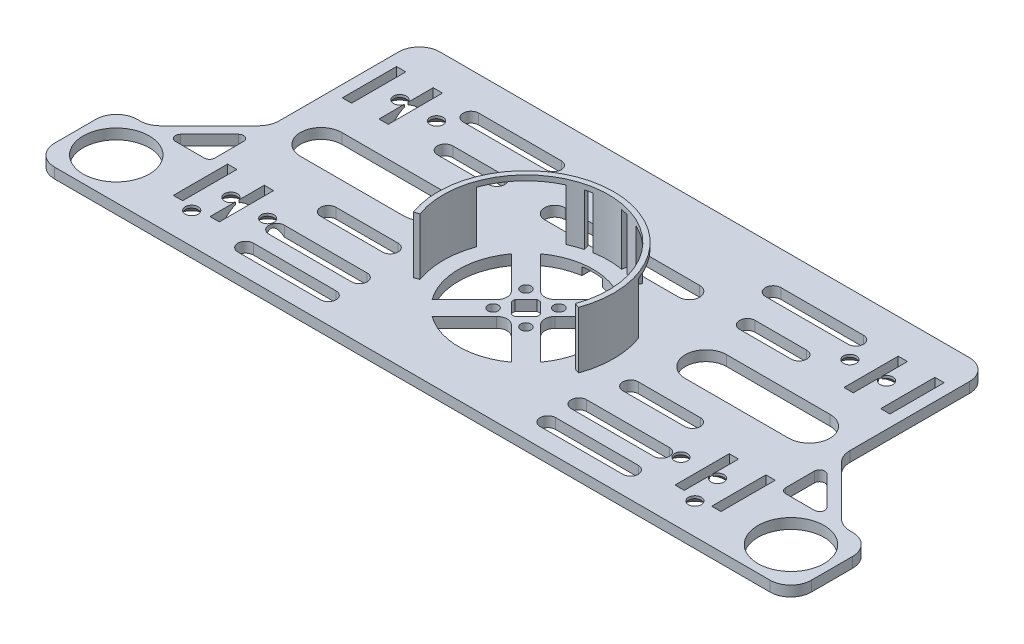
SolidWorks part; units mm, degrees
ref_plane "前视基准面" through (0, 0, 0) normal (0, 0, 1) x (1, 0, 0)
ref_plane "上视基准面" through (0, 0, 0) normal (0, 1, 0) x (1, 0, 0)
ref_plane "右视基准面" through (0, 0, 0) normal (1, 0, 0) x (0, 0, -1)
sketch "草图1" plane through (0, 0, 0) normal (0, 1, 0) x (1, 0, 0)
  line L0 (0, 0) -> (0, 46.1677) construction
  line L1 (-73.25, 0) -> (73.25, 0)
  line L2 (73.25, 0) -> (73.25, 16)
  line L8 (-73.25, 0) -> (-73.25, 16)
  line L9 (73.25, 16) -> (67.0784, 16)
  line L11 (55.25, 16) -> (55.25, 25)
  line L12 (55.25, 56.6) -> (-55.25, 56.6)
  line L13 (-55.25, 16) -> (-55.25, 25)
  line L14 (-73.25, 16) -> (-67.0784, 16)
  line L15 (64.25, 16) -> (55.25, 25)
  line L16 (67.0784, 16) -> (55.25, 27.8284)
  line L17 (55.25, 27.8284) -> (55.25, 56.6)
  line L18 (64.25, 16) -> (55.25, 16)
  line L19 (-67.0784, 16) -> (-55.25, 27.8284)
  line L20 (-64.25, 16) -> (-55.25, 25)
  line L21 (-64.25, 16) -> (-55.25, 16)
  line L22 (-55.25, 27.8284) -> (-55.25, 56.6)
  line L23 (0, 22) -> (7.4008, 22) construction
  line L24 (0, 22) -> (9.4181, 31.4181) construction
  line L25 (-10.4972, 29.6687) -> (7.6687, 11.5028)
  line L26 (10.4972, 14.3313) -> (-7.6687, 32.4972)
  line L27 (-10.4972, 14.3313) -> (7.6687, 32.4972)
  line L28 (10.4972, 29.6687) -> (-7.6687, 11.5028)
  line L29 (51.2, 17.25) -> (53, 6.75) construction
  line L30 (51.2, 17.25) -> (53, 17.25)
  line L31 (51.2, 17.25) -> (51.2, 6.75)
  line L32 (51.2, 6.75) -> (53, 6.75)
  line L33 (53, 17.25) -> (53, 6.75)
  line L34 (-51.2, 6.75) -> (-53, 6.75)
  line L35 (-53, 17.25) -> (-53, 6.75)
  line L36 (-51.2, 17.25) -> (-53, 17.25)
  line L37 (-51.2, 17.25) -> (-51.2, 6.75)
  line L38 (52.1, 0) -> (52.1, 56.6) construction
  line L39 (51.2, 49.95) -> (53, 39.45) construction
  line L40 (51.2, 49.95) -> (53, 49.95)
  line L41 (51.2, 49.95) -> (51.2, 39.45)
  line L42 (51.2, 39.45) -> (53, 39.45)
  line L43 (53, 49.95) -> (53, 39.45)
  line L44 (-51.2, 49.95) -> (-53, 39.45) construction
  line L45 (-51.2, 49.95) -> (-51.2, 39.45)
  line L46 (-51.2, 39.45) -> (-53, 39.45)
  line L47 (-53, 49.95) -> (-53, 39.45)
  line L48 (-51.2, 49.95) -> (-53, 49.95)
  line L49 (44.1, 17.25) -> (45.9, 17.25)
  line L50 (44.1, 17.25) -> (44.1, 6.75)
  line L51 (44.1, 6.75) -> (45.9, 6.75)
  line L52 (45.9, 17.25) -> (45.9, 6.75)
  line L53 (44.1, 49.95) -> (45.9, 49.95)
  line L54 (44.1, 49.95) -> (44.1, 39.45)
  line L55 (44.1, 39.45) -> (45.9, 39.45)
  line L56 (45.9, 49.95) -> (45.9, 39.45)
  line L57 (44.1, 49.95) -> (45.9, 39.45)
  line L58 (44.1, 17.25) -> (45.9, 6.75)
  line L59 (45, 56.6) -> (45, 0) construction
  line L60 (-44.1, 17.25) -> (-44.1, 6.75)
  line L61 (-44.1, 6.75) -> (-45.9, 6.75)
  line L62 (-45.9, 17.25) -> (-45.9, 6.75)
  line L63 (-44.1, 17.25) -> (-45.9, 17.25)
  line L64 (-44.1, 49.95) -> (-44.1, 39.45)
  line L65 (-44.1, 39.45) -> (-45.9, 39.45)
  line L66 (-45.9, 49.95) -> (-45.9, 39.45)
  line L67 (-44.1, 49.95) -> (-45.9, 49.95)
  line L68 (-52.1, 0) -> (-52.1, 56.6) construction
  line L69 (-45, 56.6) -> (-45, 0) construction
  line L70 (-13, 40.6) -> (13, 40.6) construction
  line L71 (-13, 42.6) -> (13, 42.6)
  line L72 (-13, 38.6) -> (13, 38.6)
  circle A2 centre (65.3, 8) radius 6.4
  circle A3 centre (-65.3, 8) radius 6.4
  circle A4 centre (0, 22) radius 4.5 construction
  circle A5 centre (3.182, 25.182) radius 1
  circle A6 centre (3.182, 18.818) radius 1
  circle A7 centre (-3.182, 18.818) radius 1
  circle A8 centre (-3.182, 25.182) radius 1
  circle A9 centre (0, 22) radius 13
  circle A11 centre (0, 22) radius 2.5
  arc A12 (-13, 42.6) -> (-13, 38.6) centre (-13, 40.6) ccw
  arc A13 (13, 38.6) -> (13, 42.6) centre (13, 40.6) ccw
  circle A14 centre (48.7, 6) radius 1
  circle A15 centre (-48.7, 6) radius 1
  point P3 (0, 56.6)
  point P18 (0, 0)
  point P19 (73.25, 8)
  point P26 (0, 22)
  point P55 (52.1, 12)
  point P66 (52.1, 44.7)
  point P67 (53, 44.7)
  point P68 (53, 12)
  point P85 (45, 44.7)
  point P100 (0, 40.6)
  dimension "D1" = 12.8
  dimension "D5" = 110.5
  dimension "D12" = 9
  dimension "D13" = 2
  dimension "D15" = 26
  dimension "D16" = 2
  dimension "D17" = 5
  dimension "D31" = 16
  dimension "D33" = 2
  dimension "D2" = 130.6
  dimension "D3" = 146.5
  dimension "D4" = 16
  dimension "D6" = 45
  dimension "D7" = 2
  dimension "D8" = 9
  dimension "D9" = 1.8
  dimension "D10" = 56.6
  dimension "D11" = 22
  dimension "D18" = 4
  dimension "D19" = 10.5
  dimension "D20" = 12
  dimension "D21" = 106
  dimension "D22" = 32.7
  dimension "D23" = 10.5
  dimension "D24" = 1.8
  dimension "D25" = 10.5
  dimension "D26" = 1.8
  dimension "D27" = 10.5
  dimension "D28" = 1.8
  dimension "D29" = 90
  dimension "D30" = 2
  dimension "D32" = 26
  dimension "D34" = 97.4
  dimension "D35" = 6
  dimension "D14" = 4
extrude "凸台-拉伸1" add sketch "草图1" along normal blind 2 contours L22 L19 L14 L8 L1 L2 L9 L16 L17 L12 A3 A2 L67 L64 L65 L66 L63 L60 L61 L62 L48 L45 L46 L47 L21 L20 L13 L15 L18 L11 L30 L33 L32 L31 L36 L37 L34 L35 L40 L43 L42 | A11 L25 L27 A9 L28 A7 | A11 L28 L25 A9 L26 A6 | A11 L26 L28 A9 L27 A5 | A11 L27 L26 A9 L25 A8 | L26 A11 | A11 L26 L27 | A11 L27 L25 | A11 L25 L28 | A11 L28 L26 | L28 A11 | L25 A11 | L27 A11
fillet "圆角1" radius 2 4 edges at (0, 1, -24.8284) (-2.8284, 1, -22) (0, 1, -19.1716) (2.8284, 1, -22)
fillet "圆角2" radius 4 10 edges at (67.0784, 1, -16) (55.25, 1, -27.8284) (-67.0784, 1, -16) (-55.25, 1, -27.8284) (-55.25, 1, -56.6) (55.25, 1, -56.6) (73.25, 1, -16) (73.25, 1, 0) (-73.25, 1, -16) (-73.25, 1, 0)
fillet "圆角3" radius 1 6 edges at (-55.25, 1, -16) (-64.25, 1, -16) (-55.25, 1, -25) (55.25, 1, -16) (55.25, 1, -25) (64.25, 1, -16)
hole_wizard "M2.5 平头机械螺钉的锥形沉头孔3" positions "草图8" profile "草图9" countersink size "M2.5" standard "ANSI Metric" end condition through all
sketch "草图8" plane through (0, 0, 0) normal (0, -1, 0) x (-1, 0, 0)
  point P0 (-47.1, 44.7)
  point P2 (-40, 44.7)
  point P4 (40, 44.7)
  point P6 (47.1, 44.7)
  point P8 (47.1, 12)
  point P10 (48.7, 6)
  point P13 (40, 12)
  point P15 (-40, 12)
  point P16 (-48.7, 6)
  point P19 (-47.1, 12)
sketch "草图9" plane through (47.1, 0, -44.7) normal (1, 0, 0) x (0, 0, -1)
  line L0 (0, 0) -> (0, 2)
  line L1 (0, 2) -> (1.25, 2)
  line L2 (1.25, 2) -> (1.25, 1.5)
  line L3 (1.25, 1.5) -> (2.75, 0)
  line L5 (2.75, 0) -> (0, 0)
  line L6 (-1.25, 1.5) -> (-2.75, 0) construction
  line L11 (0, -6.35) -> (0, 107.95) construction
  dimension "通孔孔直径" = 2.5
  dimension "通孔孔深度" = 2
  dimension "近端锥形沉头孔直径" = 5.5
  dimension "近端锥形沉头孔角度" = 90
sketch "草图10" plane through (0, 0, 0) normal (0, -1, 0) x (1, 0, 0)
  line L0 (0, 0) -> (0, -49.8475) construction
  line L1 (27.25, -29.6) -> (47.25, -29.6) construction
  line L2 (27.25, -25.6) -> (47.25, -25.6)
  line L3 (27.25, -33.6) -> (47.25, -33.6)
  line L4 (51.25, -56.6) -> (-51.25, -56.6) construction
  line L5 (55.25, -29.4853) -> (55.25, -52.6) construction
  line L6 (-27.25, -29.6) -> (-47.25, -29.6) construction
  line L7 (-27.25, -25.6) -> (-47.25, -25.6)
  line L8 (-27.25, -33.6) -> (-47.25, -33.6)
  line L9 (23.25, -19) -> (35.25, -19) construction
  line L10 (23.25, -17.5) -> (35.25, -17.5)
  line L11 (23.25, -20.5) -> (35.25, -20.5)
  line L12 (21.25, -11) -> (37.25, -11) construction
  line L13 (21.25, -9.5) -> (37.25, -9.5)
  line L14 (21.25, -12.5) -> (37.25, -12.5)
  line L15 (21.25, -5) -> (37.25, -5) construction
  line L16 (21.25, -3.5) -> (37.25, -3.5)
  line L17 (21.25, -6.5) -> (37.25, -6.5)
  line L18 (24.25, -40.6) -> (34.25, -40.6) construction
  line L19 (24.25, -39.1) -> (34.25, -39.1)
  line L20 (24.25, -42.1) -> (34.25, -42.1)
  line L21 (21.25, -48.6) -> (37.25, -48.6) construction
  line L22 (21.25, -47.1) -> (37.25, -47.1)
  line L23 (21.25, -50.1) -> (37.25, -50.1)
  line L24 (-69.25, 0) -> (69.25, 0) construction
  line L25 (-21.25, -5) -> (-37.25, -5) construction
  line L26 (-21.25, -3.5) -> (-37.25, -3.5)
  line L27 (-21.25, -6.5) -> (-37.25, -6.5)
  line L28 (-21.25, -11) -> (-37.25, -11) construction
  line L29 (-21.25, -9.5) -> (-37.25, -9.5)
  line L30 (-21.25, -12.5) -> (-37.25, -12.5)
  line L31 (-23.25, -19) -> (-35.25, -19) construction
  line L32 (-23.25, -17.5) -> (-35.25, -17.5)
  line L33 (-23.25, -20.5) -> (-35.25, -20.5)
  line L34 (-21.25, -48.6) -> (-37.25, -48.6) construction
  line L35 (-21.25, -47.1) -> (-37.25, -47.1)
  line L36 (-21.25, -50.1) -> (-37.25, -50.1)
  line L37 (-24.25, -40.6) -> (-34.25, -40.6) construction
  line L38 (-24.25, -39.1) -> (-34.25, -39.1)
  line L39 (-24.25, -42.1) -> (-34.25, -42.1)
  arc A0 (27.25, -25.6) -> (27.25, -33.6) centre (27.25, -29.6) ccw
  arc A1 (47.25, -33.6) -> (47.25, -25.6) centre (47.25, -29.6) ccw
  arc A2 (-27.25, -25.6) -> (-27.25, -33.6) centre (-27.25, -29.6) cw
  arc A3 (-47.25, -33.6) -> (-47.25, -25.6) centre (-47.25, -29.6) cw
  arc A4 (23.25, -17.5) -> (23.25, -20.5) centre (23.25, -19) ccw
  arc A5 (35.25, -20.5) -> (35.25, -17.5) centre (35.25, -19) ccw
  arc A6 (21.25, -9.5) -> (21.25, -12.5) centre (21.25, -11) ccw
  arc A7 (37.25, -12.5) -> (37.25, -9.5) centre (37.25, -11) ccw
  arc A8 (21.25, -3.5) -> (21.25, -6.5) centre (21.25, -5) ccw
  arc A9 (37.25, -6.5) -> (37.25, -3.5) centre (37.25, -5) ccw
  arc A10 (24.25, -39.1) -> (24.25, -42.1) centre (24.25, -40.6) ccw
  arc A11 (34.25, -42.1) -> (34.25, -39.1) centre (34.25, -40.6) ccw
  arc A12 (21.25, -47.1) -> (21.25, -50.1) centre (21.25, -48.6) ccw
  arc A13 (37.25, -50.1) -> (37.25, -47.1) centre (37.25, -48.6) ccw
  arc A14 (-21.25, -3.5) -> (-21.25, -6.5) centre (-21.25, -5) cw
  arc A15 (-37.25, -6.5) -> (-37.25, -3.5) centre (-37.25, -5) cw
  arc A16 (-21.25, -9.5) -> (-21.25, -12.5) centre (-21.25, -11) cw
  arc A17 (-37.25, -12.5) -> (-37.25, -9.5) centre (-37.25, -11) cw
  arc A18 (-23.25, -17.5) -> (-23.25, -20.5) centre (-23.25, -19) cw
  arc A19 (-35.25, -20.5) -> (-35.25, -17.5) centre (-35.25, -19) cw
  arc A20 (-21.25, -47.1) -> (-21.25, -50.1) centre (-21.25, -48.6) cw
  arc A21 (-37.25, -50.1) -> (-37.25, -47.1) centre (-37.25, -48.6) cw
  arc A22 (-24.25, -39.1) -> (-24.25, -42.1) centre (-24.25, -40.6) cw
  arc A23 (-34.25, -42.1) -> (-34.25, -39.1) centre (-34.25, -40.6) cw
  point P6 (37.25, -29.6)
  point P16 (29.25, -19)
  point P19 (-37.25, -29.6)
  point P30 (29.25, -11)
  point P37 (29.25, -5)
  point P44 (29.25, -40.6)
  point P51 (29.25, -48.6)
  point P62 (-29.25, -5)
  point P69 (-29.25, -11)
  point P76 (-29.25, -19)
  point P83 (-29.25, -48.6)
  point P90 (-29.25, -40.6)
  dimension "D1" = 4
  dimension "D2" = 23
  dimension "D3" = 8
  dimension "D4" = 20
  dimension "D5" = 16
  dimension "D6" = 16
  dimension "D7" = 12
  dimension "D8" = 10
  dimension "D9" = 16
  dimension "D10" = 3
  dimension "D11" = 3
  dimension "D12" = 3
  dimension "D13" = 3
  dimension "D14" = 3
  dimension "D15" = 6
  dimension "D16" = 8
  dimension "D17" = 5
  dimension "D18" = 26
  dimension "D19" = 8
  dimension "D20" = 8
extrude "切除-拉伸1" cut sketch "草图10" against normal up to surface (2 mm away) up to face at (45.7083, 2, -44.7)
sketch "草图12" plane through (0, 2, 0) normal (0, 1, 0) x (1, 0, 0)
  line L0 (0, 0) -> (0, 11.5628) construction
  line L1 (0, 22) -> (-15.9748, 16.1857)
  line L2 (0, 22) -> (-15.9748, 27.8143)
  line L3 (0, 22) -> (-7.1845, 37.4072)
  line L4 (0, 22) -> (7.1845, 37.4072)
  line L5 (0, 22) -> (15.9748, 16.1857)
  line L6 (0, 22) -> (15.9748, 27.8143)
  line L7 (0, 22) -> (-4.3999, 38.4207)
  line L8 (0, 22) -> (-2.952, 38.7417)
  line L10 (0, 22) -> (4.3999, 38.4207)
  line L11 (0, 22) -> (2.952, 38.7417)
  circle A0 centre (0, 22) radius 16
  circle A1 centre (0, 22) radius 17
  dimension "D1" = 32
  dimension "D2" = 34
  dimension "D3" = 70
  dimension "D4" = 110
  dimension "D5" = 155
  dimension "D6" = 165
  dimension "D7" = 170
extrude "凸台-拉伸2" add sketch "草图12" along normal blind 10 contours L2 A1 L1 A0 | L5 A1 L6 A0 | L7 A1 L3 A0 | A0 L0 A1 L8 | L0 A0 L11 A1 | L4 A1 L10 A0
sketch "草图13" plane through (0, 12, 0) normal (0, 1, 0) x (1, 0, 0)
  line L0 (0, 22) -> (-15.9748, 16.1857)
  line L1 (0, 0) -> (0, 14.6789) construction
  line L2 (0, 22) -> (15.9748, 16.1857)
  circle A0 centre (0, 22) radius 16
  circle A1 centre (0, 22) radius 17
  arc A2 (15.0351, 16.5277) -> (15.0351, 27.4723) centre (0, 22) ccw construction
  arc A3 (15.9748, 16.1857) -> (15.9748, 27.8143) centre (0, 22) ccw construction
  line M5 (15.0351, 16.5277) -> (15.9748, 16.1857)
  arc M6 (15.9748, 16.1857) -> (15.9748, 27.8143) centre (0, 22) ccw
  line M7 (15.9748, 27.8143) -> (15.0351, 27.4723)
  arc M8 (15.0351, 27.4723) -> (15.0351, 16.5277) centre (0, 22) cw
extrude "凸台-拉伸3" add sketch "草图13" along normal blind 1 contours L1 A0 A1 M7 | M8 M5 M6 M7 | A0 L1 A1 L0
sketch "草图14" plane through (0, 0, 0) normal (0, -1, 0) x (1, 0, 0)
  line L0 (-2, -34.8452) -> (-2, -38.6)
  line L1 (0, 0) -> (0, -51.6958) construction
  line L2 (-13, -38.6) -> (13, -38.6) construction
  line L3 (2, -34.8452) -> (2, -38.6)
  line L4 (2, -38.6) -> (-2, -38.6)
  arc A0 (-7.6687, -32.4972) -> (7.6687, -32.4972) centre (0, -22) ccw construction
  circle A1 centre (0, -22) radius 13
  arc A2 (10.4972, -29.6687) -> (10.4972, -14.3313) centre (0, -22) ccw construction
  dimension "D1" = 4
extrude "切除-拉伸2" cut sketch "草图14" against normal blind 1.5 contours A1 L1 L4 L3 | L1 A1 L0 L4
